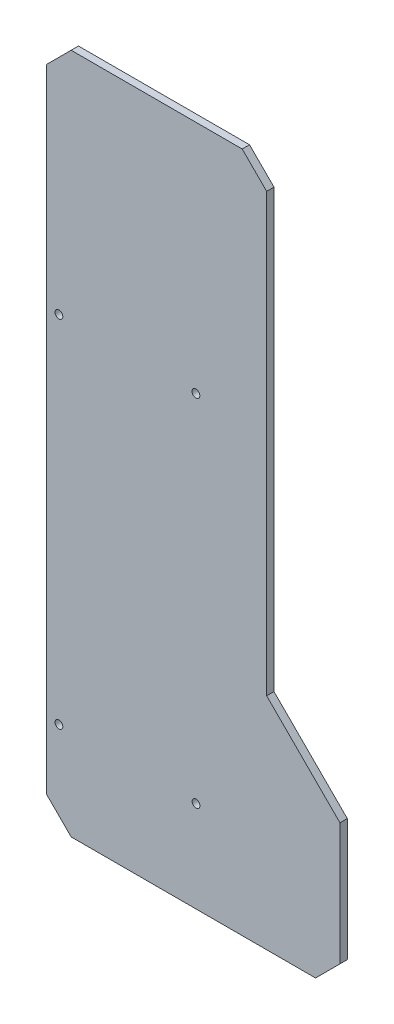
SolidWorks part; units mm, degrees
ref_plane "Front Plane" through (0, 0, 0) normal (0, 0, 1) x (1, 0, 0)
ref_plane "Top Plane" through (0, 0, 0) normal (0, 1, 0) x (1, 0, 0)
ref_plane "Right Plane" through (0, 0, 0) normal (1, 0, 0) x (0, 0, -1)
sketch "Sketch1" plane through (0, 0, 0) normal (0, 0, 1) x (1, 0, 0)
  line L0 (-80, -0.7565) -> (-80, 4.2435) construction
  line L1 (-70, 99.0079) -> (0, 99.0079)
  line L2 (-80, 89.0079) -> (-80, -169.754)
  line L3 (-70, -179.754) -> (0, -179.754)
  line L5 (-54.5, 99.0079) -> (-57.5, 99.0079) construction
  line L6 (-13.5618, -149.754) -> (-80, -149.754) construction
  line L8 (10, -89.754) -> (10, 89.0079)
  line L9 (-80, 89.0079) -> (-70, 99.0079)
  line L10 (10, 89.0079) -> (0, 99.0079)
  line L11 (-80, -169.754) -> (-70, -179.754)
  line L13 (10, -89.754) -> (40, -119.754)
  line L14 (40, -119.754) -> (40, -169.754)
  line L15 (30, -179.754) -> (0, -179.754)
  line L16 (40, -169.754) -> (30, -179.754)
  circle A0 centre (-75, 2.8935) radius 1.6
  circle A1 centre (-18.9466, 2.8935) radius 1.6
  circle A2 centre (-75, -142.404) radius 1.6
  circle A3 centre (-18.8932, -142.404) radius 1.6
  point P0 (-80, 99.0079)
  point P2 (-80, -179.754)
  point P12 (10, 99.0079)
  point P32 (40, -179.754)
  dimension "D2" = 3.2
  dimension "D1" = 30
  dimension "D3" = 90
  dimension "D4" = 45
  dimension "D7" = 60
  dimension "D10" = 30
extrude "Extrude1" add sketch "Sketch1" along normal blind 3
